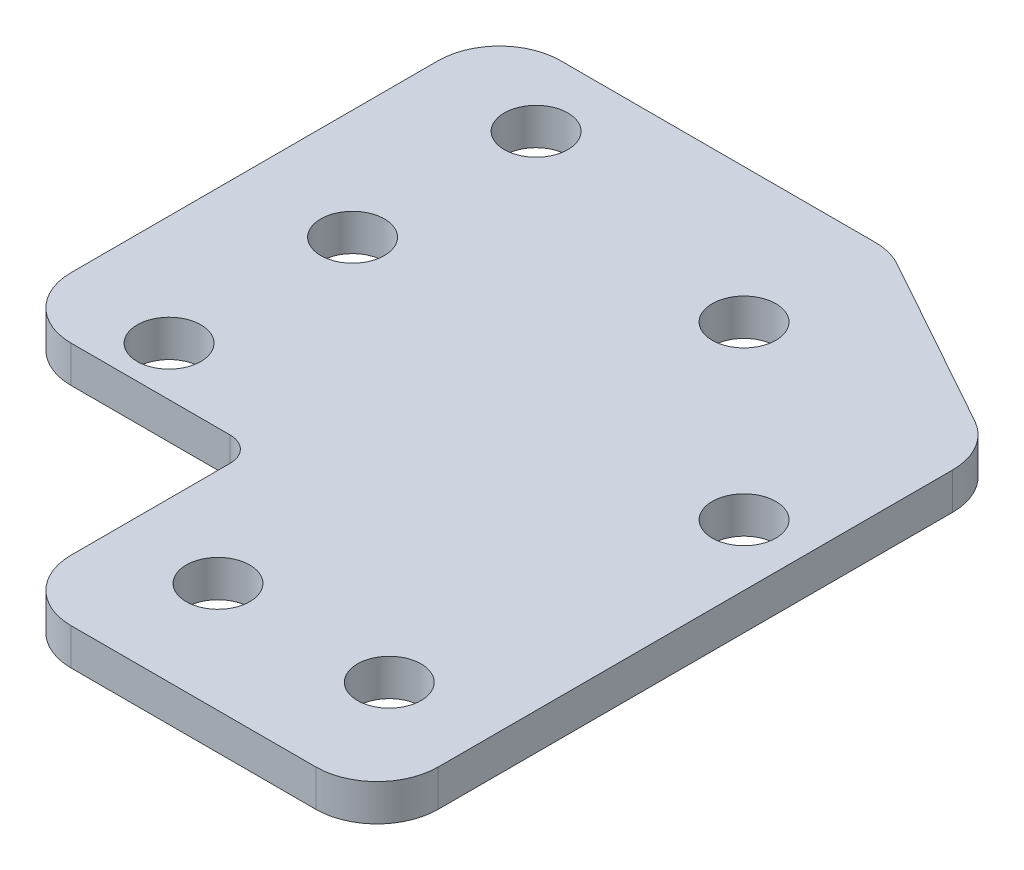
SolidWorks part; units mm, degrees
material "AISI 4340 Steel, annealed"
ref_plane "Front Plane" through (0, 0, 0) normal (0, 0, 1) x (1, 0, 0)
ref_plane "Top Plane" through (0, 0, 0) normal (0, 1, 0) x (1, 0, 0)
ref_plane "Right Plane" through (0, 0, 0) normal (1, 0, 0) x (0, 0, -1)
sketch "Sketch2" plane through (0, 0, 0) normal (0, 1, 0) x (1, 0, 0)
  line L3 (0, 60) -> (32, 60)
  line L4 (32, 60) -> (50, 50)
  line L5 (50, 50) -> (50, 0)
  line L6 (50, 0) -> (20, 0)
  line L7 (9, 60) -> (9, 20) construction
  line L9 (20, 0) -> (20, 20)
  line L10 (20, 20) -> (0, 20)
  line L11 (0, 20) -> (0, 60)
  line L12 (20, 9) -> (50, 9) construction
  circle A0 centre (9, 39) radius 2.6
  circle A1 centre (9, 24) radius 2.6
  circle A2 centre (28, 9) radius 2.6
  circle A3 centre (42, 9) radius 2.6
  circle A5 centre (9, 54) radius 2.6
  point P8 (35, 0)
  dimension "D9" = 8
  dimension "D2" = 9
  dimension "D4" = 30
  dimension "D11" = 5.2
  dimension "D3" = 9
  dimension "D5" = 32
  dimension "D6" = 50
  dimension "D7" = 40
  dimension "D8" = 15
  dimension "D10" = 15
  dimension "D12" = 20
  dimension "D13" = 14
  dimension "D14" = 20
base flange "Base-Flange1" sketch "Sketch2" thickness 3 reverse thickness direction no parameters "D1"=5
fillet "Fillet1" radius 5 6 edges at (32, -1.5, -60) (50, -1.5, -50) (50, -1.5, 0) (20, -1.5, 0) (0, -1.5, -20) (0, -1.5, -60)
sketch "Sketch3" plane through (0, 0, 0) normal (0, 1, 0) x (1, 0, 0)
  line L0 (25, 0) -> (45, 0) construction
  line L1 (0, 55) -> (0, 25) construction
  line L2 (60.0632, 20) -> (-12.6245, 20) construction
  line L3 (20, -5.5154) -> (20, 83.5832) construction
  line L4 (25, 0) -> (45, 0) construction
  circle A0 centre (45, 35) radius 2.6
  circle A1 centre (31, 49) radius 2.6
  circle A2 centre (45, 35) radius 8.5 construction
  circle A3 centre (31, 49) radius 8.5 construction
  dimension "D1" = 5.2
  dimension "D6" = 17
  dimension "D2" = 35
  dimension "D3" = 45
  dimension "D4" = 14
  dimension "D5" = 14
  dimension "D7" = 20
  dimension "D8" = 20
extrude "Cut-Extrude1" cut sketch "Sketch3" against normal blind 10 normal cut yes
fillet "Fillet2" radius 2 1 edges at (20, -1.5, -20)
sketch "Bend-Lines1" [suppressed] plane through (0, 0, 0) normal (0, 1, 0) x (1, 0, 0)
sketch "Bounding-Box1" [suppressed] plane through (0, 0, 0) normal (0, 1, 0) x (1, 0, 0)
sheet metal parameters "Sheet-Metal3" thickness 3 parameters "D1"=5
flat pattern "Flat-Pattern3" [suppressed]
sketch "Bend-Lines2" plane through (0, 0, 0) normal (0, 1, 0) x (1, 0, 0)
sketch3d "Bounding-Box2" [suppressed]
  line L0 (0, 50, 0) -> (50, 50, 0) construction
  line L1 (0, 0, 0) -> (50, 0, 0) construction
  line L2 (0, 50, 0) -> (0, 0, 0) construction
  line L3 (50, 50, 0) -> (50, 0, 0) construction
sheet metal parameters "Sheet-Metal4" thickness 3 parameters "D1"=5
flat pattern "Flat-Pattern3"
sketch "Bend-Lines2" plane through (0, 0, 0) normal (0, 1, 0) x (1, 0, 0)
sketch3d "Bounding-Box2" [suppressed]
  line L0 (50, 60, 0) -> (50, 0, 0) construction
  line L1 (0, 60, 0) -> (0, 0, 0) construction
  line L2 (50, 60, 0) -> (0, 60, 0) construction
  line L3 (50, 0, 0) -> (0, 0, 0) construction
